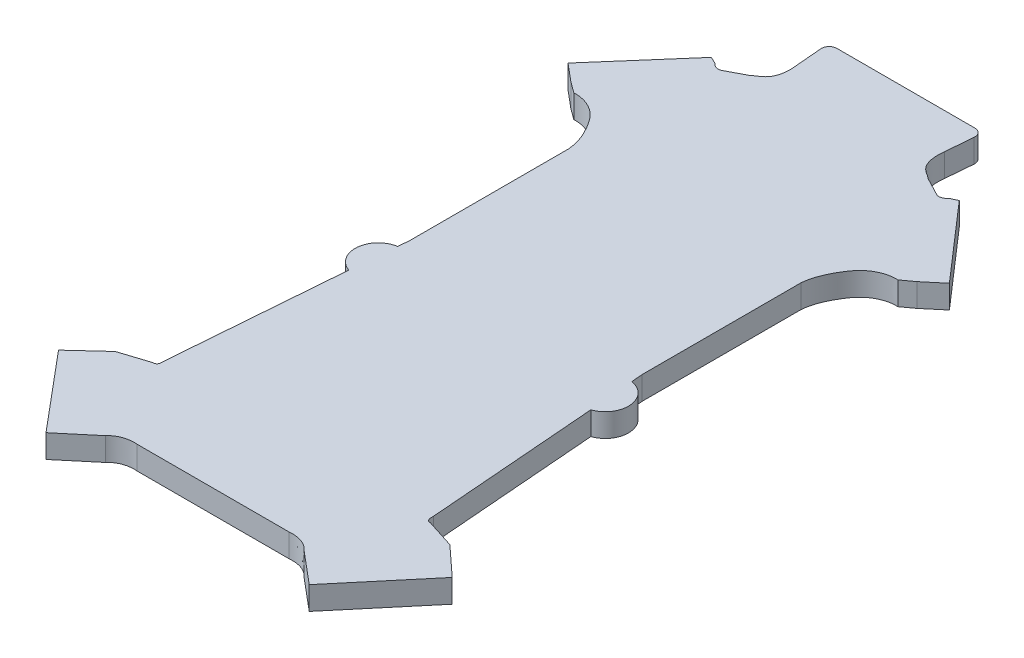
SolidWorks part; units mm, degrees
ref_plane "Front Plane" through (0, 0, 0) normal (0, 0, 1) x (1, 0, 0)
ref_plane "Top Plane" through (0, 0, 0) normal (0, 1, 0) x (1, 0, 0)
ref_plane "Right Plane" through (0, 0, 0) normal (1, 0, 0) x (0, 0, -1)
sketch "Sketch1" plane through (0, 0, 0) normal (0, 1, 0) x (1, 0, 0)
  line L1 (0, 0) -> (200, 0)
  line L2 (0, 0) -> (0, 200)
  line L3 (0, 200) -> (200, 200)
  line L4 (200, 0) -> (200, 200)
  dimension "D1" = 200
  dimension "D2" = 200
extrude "Boss-Extrude1" add sketch "Sketch1" along normal blind 6
sketch "Sketch2" plane through (0, 0, 0) normal (0, -1, 0) x (1, 0, 0)
  line L0 (142.4703, -38.4743) -> (138.9806, -82.5678)
  line L1 (75.6673, -176.9941) -> (77.5555, -176.1314)
  line L2 (137.9654, -94.1709) -> (137.7139, -97.0459)
  line L3 (137.7139, -97.0459) -> (137.7139, -138.1223)
  line L4 (58.4416, -157.2184) -> (75.6673, -176.9941)
  line L5 (127.3459, -16.2435) -> (88.0819, -16.2435)
  line L6 (63.0007, -153.3929) -> (58.4416, -157.2184)
  line L7 (65.8461, -151.3141) -> (63.0007, -153.3929)
  line L9 (71.8743, -36.5483) -> (64.4781, -34.1729)
  line L12 (135.7008, -175.3246) -> (130.8536, -177.8581)
  line L13 (64.4781, -34.1729) -> (56.8447, -27.1502)
  line L14 (126.927, -186.0703) -> (127.5212, -193.0744)
  line L15 (125.5284, -195.2435) -> (89.8994, -195.2435)
  line L16 (107.7139, -204.2017) -> (107.7139, -16.2435) construction
  line L19 (56.8447, -27.1502) -> (73.7024, -7.0599)
  line L20 (73.7024, -7.0599) -> (82.0719, -14.0827)
  line L24 (88.5008, -186.0703) -> (87.9066, -193.0744)
  line L26 (79.727, -175.3246) -> (84.5742, -177.8581)
  line L31 (77.7139, -97.0459) -> (77.7139, -138.1223)
  line L34 (77.4624, -94.1709) -> (77.7139, -97.0459)
  line L36 (72.9576, -38.4743) -> (76.4473, -82.5678)
  line L37 (141.7254, -7.0599) -> (133.356, -14.0827)
  line L38 (158.5831, -27.1502) -> (141.7254, -7.0599)
  line L39 (150.9497, -34.1729) -> (158.5831, -27.1502)
  line L40 (143.5536, -36.5483) -> (150.9497, -34.1729)
  line L41 (200, -200) -> (0, -200) construction
  line L45 (149.5817, -151.3141) -> (152.4271, -153.3929)
  line L46 (152.4271, -153.3929) -> (156.9863, -157.2184)
  line L47 (156.9863, -157.2184) -> (139.7605, -176.9941)
  line L48 (139.7605, -176.9941) -> (137.8723, -176.1314)
  line L54 (0, -200) -> (200, -200)
  line L55 (200, -200) -> (200, 0)
  line L56 (200, 0) -> (0, 0)
  line L57 (0, 0) -> (0, -200)
  arc A0 (137.9654, -94.1709) -> (138.9806, -82.5678) centre (137.0348, -88.2435) ccw
  arc A3 (127.5212, -193.0744) -> (125.5284, -195.2435) centre (125.5284, -193.2435) cw
  arc A4 (135.7008, -175.3246) -> (137.8723, -176.1314) centre (136.2187, -177.2564) cw
  arc A6 (79.727, -175.3246) -> (77.5555, -176.1314) centre (79.2091, -177.2564) ccw
  arc A7 (87.9066, -193.0744) -> (89.8994, -195.2435) centre (89.8994, -193.2435) ccw
  arc A8 (77.4624, -94.1709) -> (76.4473, -82.5678) centre (78.393, -88.2435) cw
  spline S0 degree 3 poles (77.7139, -138.1223) (77.5169, -140.6987) (75.9201, -144.4578) (72.9381, -148.8728) (69.4779, -150.9496) (67.0839, -151.3752) (65.8461, -151.3141) knots 0 0 0 0 0.390118 0.632218 0.808161 1 1 1 1
  spline S1 degree 3 poles (71.8743, -36.5483) (73.0299, -36.4607) (72.9809, -37.7548) (72.9576, -38.4743) knots 0 0 0 0 1 1 1 1
  spline S2 degree 3 poles (130.8536, -177.8581) (130.0758, -178.5464) (126.9168, -179.9629) (126.6337, -184.0704) (126.927, -186.0703) knots 0 0 0 0 0.321172 1 1 1 1
  spline S3 degree 3 poles (82.0719, -14.0827) (83.5315, -15.7971) (85.9091, -16.4555) (88.0819, -16.2435) knots 0 0 0 0 1 1 1 1
  spline S4 degree 3 poles (84.5742, -177.8581) (85.352, -178.5464) (88.511, -179.9629) (88.7941, -184.0704) (88.5008, -186.0703) knots 0 0 0 0 0.321172 1 1 1 1
  spline S6 degree 3 poles (133.356, -14.0827) (131.8963, -15.7971) (129.5188, -16.4555) (127.3459, -16.2435) knots 0 0 0 0 1 1 1 1
  spline S9 degree 3 poles (143.5536, -36.5483) (142.3979, -36.4607) (142.4469, -37.7548) (142.4703, -38.4743) knots 0 0 0 0 1 1 1 1
  spline S10 degree 3 poles (137.7139, -138.1223) (137.911, -140.6987) (139.5077, -144.4578) (142.4897, -148.8728) (145.95, -150.9496) (148.3439, -151.3752) (149.5817, -151.3141) knots 0 0 0 0 0.390118 0.632218 0.808161 1 1 1 1
  point P60 (87.7226, -195.2435)
  point P61 (68.5442, -35.3606)
  point P63 (0, 0)
  point P64 (0, 0)
  point P67 (107.8274, -195.2435)
  point P68 (107.7139, -204.2017)
  point P69 (107.7139, -204.2017)
  point P70 (107.7139, -195.2435)
  point P71 (0, 0)
  point P72 (137.0348, -88.2435)
  point P73 (138.5858, -82.5678)
  point P90 (146.8837, -35.3606)
  point P104 (127.7053, -195.2435)
  dimension "D1" = 2
  dimension "D5" = 9.844
  dimension "D13" = 19.4393
  dimension "D21" = 6
  dimension "D36" = 2
  dimension "D45" = 6.6347
  dimension "D3" = 19.8073
  dimension "D4" = 19.2131
  dimension "D6" = 2.5103
  dimension "D7" = 23.1397
  dimension "D8" = 27.9869
  dimension "D9" = 30.1584
  dimension "D10" = 32.0466
  dimension "D11" = 26.226
  dimension "D12" = 41.8678
  dimension "D14" = 41.0531
  dimension "D15" = 38.2162
  dimension "D16" = 35.2981
  dimension "D17" = 32.4479
  dimension "D18" = 30.8719
  dimension "D19" = 30
  dimension "D20" = 41.0764
  dimension "D22" = 29.3209
  dimension "D23" = 2.886
  dimension "D24" = 30.2515
  dimension "D25" = 31.2667
  dimension "D26" = 4.7565
  dimension "D27" = 92.2861
  dimension "D28" = 19.9913
  dimension "D29" = 7.0041
  dimension "D30" = 2.1691
  dimension "D31" = 17.8145
  dimension "D32" = 19.1485
  dimension "D33" = 2.6543
  dimension "D34" = 3.6822
  dimension "D35" = 20.6294
  dimension "D37" = 2.076
  dimension "D38" = 34.7563
  dimension "D39" = 1.5163
  dimension "D40" = 7.7682
  dimension "D41" = 2.3754
  dimension "D42" = 7.0228
  dimension "D43" = 20.0903
  dimension "D44" = 26.226
  dimension "D46" = 10.9255
  dimension "D47" = 7.0599
  dimension "D48" = 2.2761
  dimension "D49" = 2.6379
  dimension "D50" = 1.5809
  dimension "D51" = 19.632
extrude "Cut-Extrude2" cut sketch "Sketch2" against normal through all both and the other way through all
